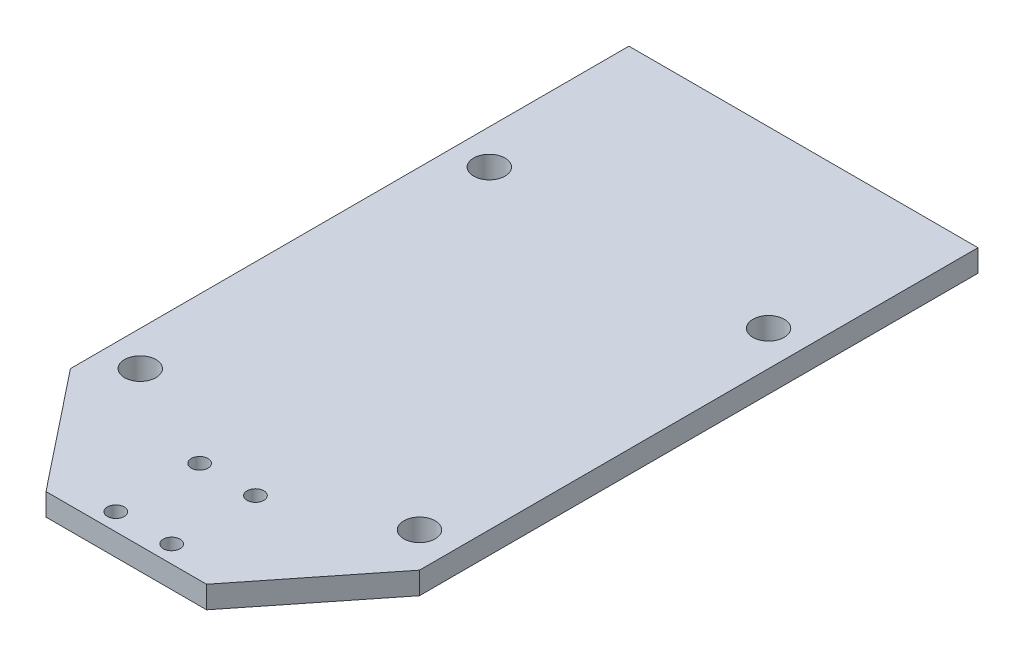
SolidWorks part; units mm, degrees
material "6061-T6 (SS)"
ref_plane "Front Plane" through (0, 0, 0) normal (0, 0, 1) x (1, 0, 0)
ref_plane "Top Plane" through (0, 0, 0) normal (0, 1, 0) x (1, 0, 0)
ref_plane "Right Plane" through (0, 0, 0) normal (1, 0, 0) x (0, 0, -1)
sketch "Sketch1" plane through (0, 0, 0) normal (0, 1, 0) x (1, 0, 0)
  line L0 (-11.5, -57) -> (-25, -40)
  line L1 (25, -40) -> (-25, -40)
  line L2 (25, -40) -> (25, 40)
  line L3 (25, 40) -> (-25, 40)
  line L4 (-25, -40) -> (-25, 40)
  line L5 (25, -40) -> (-25, 40) construction
  line L6 (25, 40) -> (-25, -40) construction
  line L7 (-11.5, -40) -> (11.5, -40)
  line L8 (-11.5, -40) -> (-11.5, -57)
  line L9 (-11.5, -57) -> (11.5, -57)
  line L10 (11.5, -40) -> (11.5, -57)
  line L11 (11.5, -57) -> (25, -40)
  line L12 (-25, -40) -> (25, -40)
  line L13 (11.5, -57) -> (-11.5, -57)
  point P0 (0, 0)
  dimension "D1" = 80
  dimension "D2" = 50
  dimension "D3" = 23
  dimension "D4" = 17
  dimension "D5" = 13.5
extrude "Boss-Extrude1" add sketch "Sketch1" along normal mid plane 3.175 contours L8 L1 L0 | L10 L11 L1 | L4 L1 L2 L3 | L10 L1 L8 L9 region at (-16, 0, 45.6667) region at (0, 0, 48.5) region at (0, 0, 0) region at (16, 0, 45.6667)
sketch "Sketch4" plane through (0, 1.5875, 0) normal (0, 1, 0) x (1, 0, 0)
  line L0 (-11.5, -57) -> (11.5, -57) construction
  point P0 (-4, -54.5)
  point P2 (4, -54.5)
  point P4 (4, -42.5)
  point P6 (-4, -42.5)
  point P16 (0, -57)
  dimension "D1" = 8
  dimension "D2" = 12
  dimension "D3" = 4
  dimension "D4" = 2.5
hole_wizard "M2 Clearance Hole1" positions "Sketch4" profile "Sketch3" hole size "M2" standard "ANSI Metric" end condition through all
sketch "Sketch3" plane through (-4, 1.5875, 54.5) normal (1, 0, 0) x (0, 0, 1)
  line L0 (0, 0) -> (0, 3.175)
  line L1 (0, 3.175) -> (1.2, 3.175)
  line L2 (1.2, 3.175) -> (1.2, 0)
  line L5 (1.2, 0) -> (0, 0)
  line L11 (0, -6.35) -> (0, 107.95) construction
  dimension "Thru Hole Dia." = 2.4
  dimension "Thru Hole Depth" = 3.175
sketch "Sketch7" plane through (0, 1.5875, 0) normal (0, 1, 0) x (1, 0, 0)
  line L0 (-25, -40) -> (-25, 40) construction
  line L1 (25, -40) -> (25, 40) construction
  line L2 (25, 40) -> (-25, 40) construction
  point P0 (-20, 15)
  point P2 (20, 15)
  point P4 (20, -35)
  point P6 (-20, -35)
  dimension "D1" = 5
  dimension "D2" = 5
  dimension "D3" = 25
  dimension "D4" = 50
hole_wizard "M4 Clearance Hole1" positions "Sketch7" profile "Sketch6" hole size "M4" standard "ANSI Metric" end condition through all
sketch "Sketch6" plane through (-20, 1.5875, -15) normal (1, 0, 0) x (0, 0, 1)
  line L0 (0, 0) -> (0, 3.175)
  line L1 (0, 3.175) -> (2.25, 3.175)
  line L2 (2.25, 3.175) -> (2.25, 0)
  line L5 (2.25, 0) -> (0, 0)
  line L11 (0, -6.35) -> (0, 107.95) construction
  dimension "Thru Hole Dia." = 4.5
  dimension "Thru Hole Depth" = 3.175
